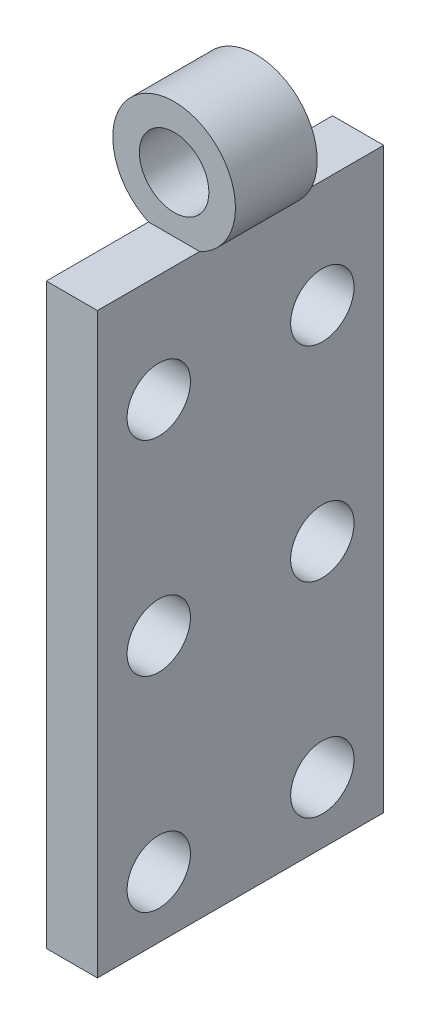
SolidWorks part; units mm, degrees
ref_plane "Front Plane" through (0, 0, 0) normal (0, 0, 1) x (1, 0, 0)
ref_plane "Top Plane" through (0, 0, 0) normal (0, 1, 0) x (1, 0, 0)
ref_plane "Right Plane" through (0, 0, 0) normal (1, 0, 0) x (0, 0, -1)
sketch "Sketch2" plane through (0, 0, 0) normal (0, 0, 1) x (1, 0, 0)
  line L0 (0, 0) -> (0, 24076.8791) construction
  line L1 (0, 0) -> (24076.8791, 0) construction
  line L2 (0, 10) -> (24076.8791, 10) construction
  line L3 (0, 18) -> (24076.8791, 18) construction
  line L4 (0, 21) -> (24076.8791, 21) construction
  line L5 (1.25, 0) -> (1.25, 50000) construction
  line L6 (-1.25, 0) -> (-1.25, 50000) construction
  line L7 (-1.25, -13) -> (1.25, -13) construction
  line L13 (-1.25, -13) -> (1.25, -13)
  line L14 (-1.25, -13) -> (-1.25, 15.2728)
  line L15 (-1.25, 15.2728) -> (1.25, 15.2728)
  line L16 (1.25, -13) -> (1.25, 15.2728)
  circle A0 centre (0, 18) radius 3
  dimension "D4" = 6
  dimension "D1" = 10
  dimension "D2" = 8
  dimension "D3" = 3
  dimension "D5" = 0
  dimension "D6" = 1.25
  dimension "D7" = 13
extrude "Boss-Extrude5" add sketch "Sketch2" along normal mid plane 14 contours L16 L15 L14 L13
extrude "Boss-Extrude6" add sketch "Sketch2<8>" along normal mid plane 4 contours A0
sketch "Sketch2<8>" plane through (0, 0, 0) normal (0, 0, 1) x (1, 0, 0) same geometry as "Sketch2"
sketch "Sketch3" plane through (0, 0, 2) normal (0, 0, 1) x (1, 0, 0)
  circle A0 centre (0, 18) radius 1.7
  dimension "D1" = 3.4
extrude "Cut-Extrude1" cut sketch "Sketch3" against normal through all
sketch "Sketch4" plane through (1.25, 0, 0) normal (1, 0, 0) x (0, 0, -1)
  line L0 (0, 0) -> (50000, 0) construction
  line L1 (0, 10) -> (50000, 10) construction
  line L3 (0, -13) -> (0, 15.2728) construction
  circle A0 centre (4, 0) radius 1.55
  circle A1 centre (-4, 0) radius 1.55
  circle A2 centre (-4, 10) radius 1.55
  circle A3 centre (4, 10) radius 1.55
  circle A4 centre (4, -10) radius 1.55
  circle A5 centre (-4, -10) radius 1.55
  dimension "D3" = 3.1
  dimension "D4" = 3.1
  dimension "D7" = 3.1
  dimension "D9" = 3.1
  dimension "D1" = 10
  dimension "D2" = 4
  dimension "D5" = 8
  dimension "D6" = 4
  dimension "D8" = 8
extrude "Cut-Extrude2" cut sketch "Sketch4" against normal through all
